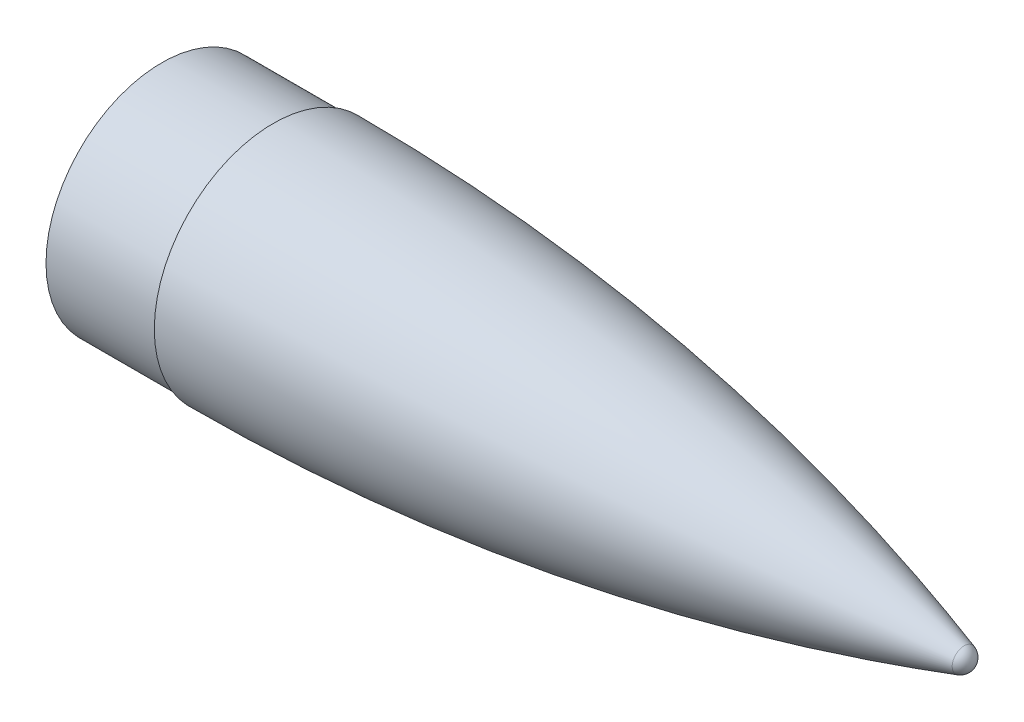
SolidWorks part; units mm, degrees
ref_plane "前基準面" through (0, 0, 0) normal (0, 0, 1) x (1, 0, 0)
ref_plane "上基準面" through (0, 0, 0) normal (0, 1, 0) x (1, 0, 0)
ref_plane "右基準面" through (0, 0, 0) normal (1, 0, 0) x (0, 0, -1)
sketch "草圖2" plane through (0, 0, 0) normal (0, 0, 1) x (1, 0, 0)
  line L0 (-558.8, 95) -> (-558.8, 85)
  line L3 (-711, 0) -> (126.4299, 0) construction
  line L4 (0, 26.965) -> (0, -35.3928) construction
  line L5 (-558.8, 95) -> (-39.4127, 95) construction
  line L6 (-10, 0) -> (0, 0)
  line L7 (-647.8, 80) -> (-558.8, 80)
  line L8 (-647.8, 80) -> (-647.8, 92.5)
  line L9 (-647.8, 92.5) -> (-558.8, 92.5)
  line L10 (-558.8, 80) -> (-558.8, 92.5)
  line L11 (-647.8, 80) -> (-558.8, 92.5) construction
  line L12 (-647.8, 92.5) -> (-558.8, 80) construction
  arc A1 (0, 0) -> (-6.9749, 9.5315) centre (-10, 0) ccw
  arc A2 (-6.9749, 9.5315) -> (-558.8, 95) centre (-558.8, -1729.1555) ccw
  arc A3 (-10, 0) -> (-558.8, 85) centre (-558.8, -1729.1555) ccw
  point P4 (-603.3, 86.25)
  dimension "D3" = 10
  dimension "D1" = 95
  dimension "D2" = 558.8
  dimension "D5" = 170
  dimension "D6" = 89
  dimension "D7" = 185
  dimension "D8" = 160
  dimension "D4" = 10
revolve "旋轉1" add sketch "草圖2" angle 360 about L3 region at (-280.4652, 67.9048, 0) region at (-603.3, 86.25, 0)
